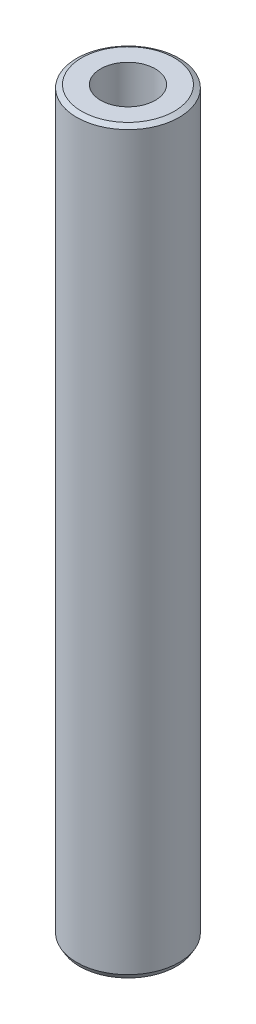
SolidWorks part; units mm, degrees
ref_plane "Front Plane" through (0, 0, 0) normal (0, 0, 1) x (1, 0, 0)
ref_plane "Top Plane" through (0, 0, 0) normal (0, 1, 0) x (1, 0, 0)
ref_plane "Right Plane" through (0, 0, 0) normal (1, 0, 0) x (0, 0, -1)
sketch "Sketch1" plane through (0, 0, 0) normal (0, 1, 0) x (1, 0, 0)
  circle A0 centre (0, 0) radius 20
  dimension "SHAFT_OD" = 40
extrude "Boss-Extrude1" add sketch "Sketch1" along normal blind 288.7195
sketch "Sketch2" plane through (0, 0, 0) normal (0, 1, 0) x (1, 0, 0)
  circle A0 centre (0, 0) radius 10.6689
  dimension "BORE_D" = 21.3378
extrude "Cut-Extrude1" cut sketch "Sketch2" along normal through all
chamfer "Chamfer1" distance 1.1021 angle 60 2 edges at (0, 288.7195, 20) (0, 0, 20) first distance on face at (0, 288.7195, 20) first distance on face at (0, 0, 10.6689)
